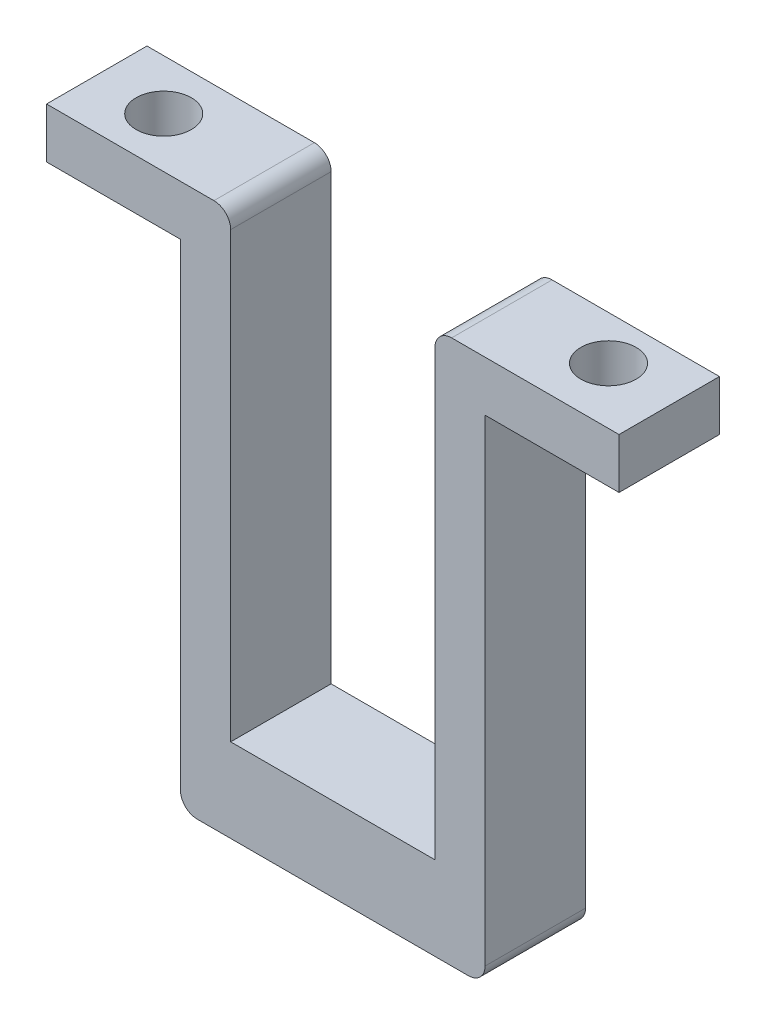
SolidWorks part; units mm, degrees
ref_plane "Front Plane" through (0, 0, 0) normal (0, 0, 1) x (1, 0, 0)
ref_plane "Top Plane" through (0, 0, 0) normal (0, 1, 0) x (1, 0, 0)
ref_plane "Right Plane" through (0, 0, 0) normal (1, 0, 0) x (0, 0, -1)
sketch "Sketch6" plane through (0, 0, 0) normal (0, 0, 1) x (1, 0, 0)
  line L0 (-6.1, 0) -> (6.1, 0)
  line L1 (6.1, 0) -> (6.1, 27.5)
  line L2 (6.1, 27.5) -> (17.1, 27.5)
  line L3 (17.1, 27.5) -> (17.1, 24.5)
  line L4 (17.1, 24.5) -> (9.1, 24.5)
  line L5 (9.1, 24.5) -> (9.1, -5)
  line L6 (9.1, -5) -> (-9.1, -5)
  line L7 (0, 4.2064) -> (0, -6.4903) construction
  line L8 (-9.1, 24.5) -> (-9.1, -5)
  line L9 (-17.1, 24.5) -> (-9.1, 24.5)
  line L10 (-17.1, 27.5) -> (-17.1, 24.5)
  line L11 (-6.1, 27.5) -> (-17.1, 27.5)
  line L12 (-6.1, 0) -> (-6.1, 27.5)
  point P12 (0, -5)
  point P17 (0, 0)
  dimension "D1" = 6.1
  dimension "D2" = 32.5
  dimension "D3" = 3
  dimension "D4" = 3
  dimension "D5" = 11
  dimension "D6" = 5
extrude "Boss-Extrude5" add sketch "Sketch6" along normal blind 6
sketch "Sketch7" plane through (0, 24.5, 0) normal (0, -1, 0) x (1, 0, 0)
  line L0 (-9.1, 6) -> (-9.1, 0) construction
  line L1 (9.1, 6) -> (9.1, 0) construction
  line L2 (-17.1, 6) -> (-9.1, 6) construction
  circle A0 centre (-13.1, 3) radius 1.65
  circle A1 centre (13.1, 2.6286) radius 1.65
  dimension "D1" = 3.3
  dimension "D2" = 3.3
  dimension "D3" = 4
  dimension "D4" = 4
  dimension "D5" = 3
extrude "Cut-Extrude2" cut sketch "Sketch7" against normal up to surface (3 mm away) up to face at (-11.6, 27.5, 3)
fillet "Fillet1" radius 1 2 edges at (-6.1, 27.5, 3) (6.1, 27.5, 3)
fillet "Fillet2" radius 1 2 edges at (9.1, -5, 3) (-9.1, -5, 3)
equation "\"D2@Sketch7\"=\"D1@Sketch7\""
equation "\"D4@Sketch7\"=\"D3@Sketch7\""
